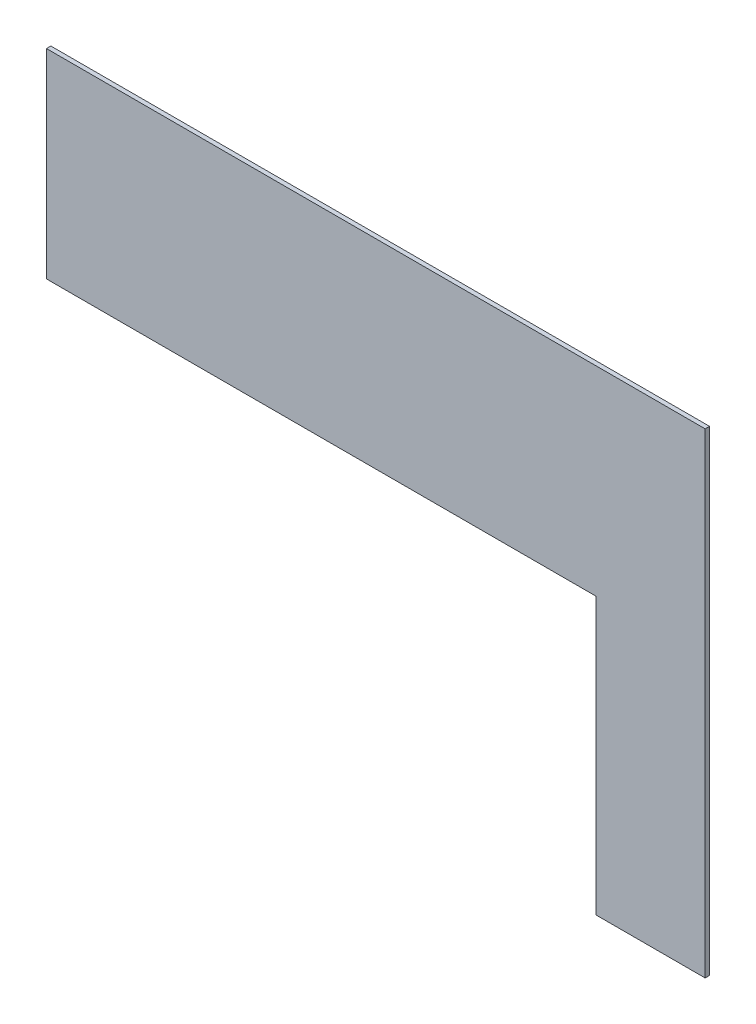
SolidWorks part; units mm, degrees
ref_plane "Ön Düzlem" through (0, 0, 0) normal (0, 0, 1) x (1, 0, 0)
ref_plane "Üst Düzlem" through (0, 0, 0) normal (0, 1, 0) x (1, 0, 0)
ref_plane "Sağ Düzlem" through (0, 0, 0) normal (1, 0, 0) x (0, 0, -1)
sketch "Çizim1" plane through (0, 0, 0) normal (0, 0, 1) x (1, 0, 0)
  line L0 (0, 0) -> (1205, 0)
  line L1 (1205, 0) -> (1205, -870)
  line L2 (1205, -870) -> (1005, -870)
  line L3 (1005, -870) -> (1005, -365)
  line L4 (1005, -365) -> (0, -365)
  line L5 (0, -365) -> (0, 0)
  dimension "D1" = 365
  dimension "D2" = 1005
  dimension "D3" = 505
  dimension "D4" = 200
base flange "Taban-Flanş1" sketch "Çizim1" thickness 8 reverse thickness direction no parameters "D1"=2.5
sketch "Büküm-Çizgileri1" [suppressed] plane through (0, 0, 0) normal (0, 1, 0) x (1, 0, 0)
sketch "Sınırlandırma-Kutusu1" [suppressed] plane through (0, 0, 0) normal (0, 1, 0) x (1, 0, 0)
sheet metal parameters "Sac-Levha1" thickness 8 parameters "D1"=2.5
flat pattern "Düz-Çoğaltma1" [suppressed]
sketch "Büküm-Çizgileri2" plane through (0, 0, 0) normal (0, 1, 0) x (1, 0, 0)
sketch3d "Sınırlandırma-Kutusu2" [suppressed]
  line L0 (0, -870, 0) -> (1205, -870, 0) construction
  line L1 (0, 0, 0) -> (1205, 0, 0) construction
  line L2 (0, -870, 0) -> (0, 0, 0) construction
  line L3 (1205, -870, 0) -> (1205, 0, 0) construction
